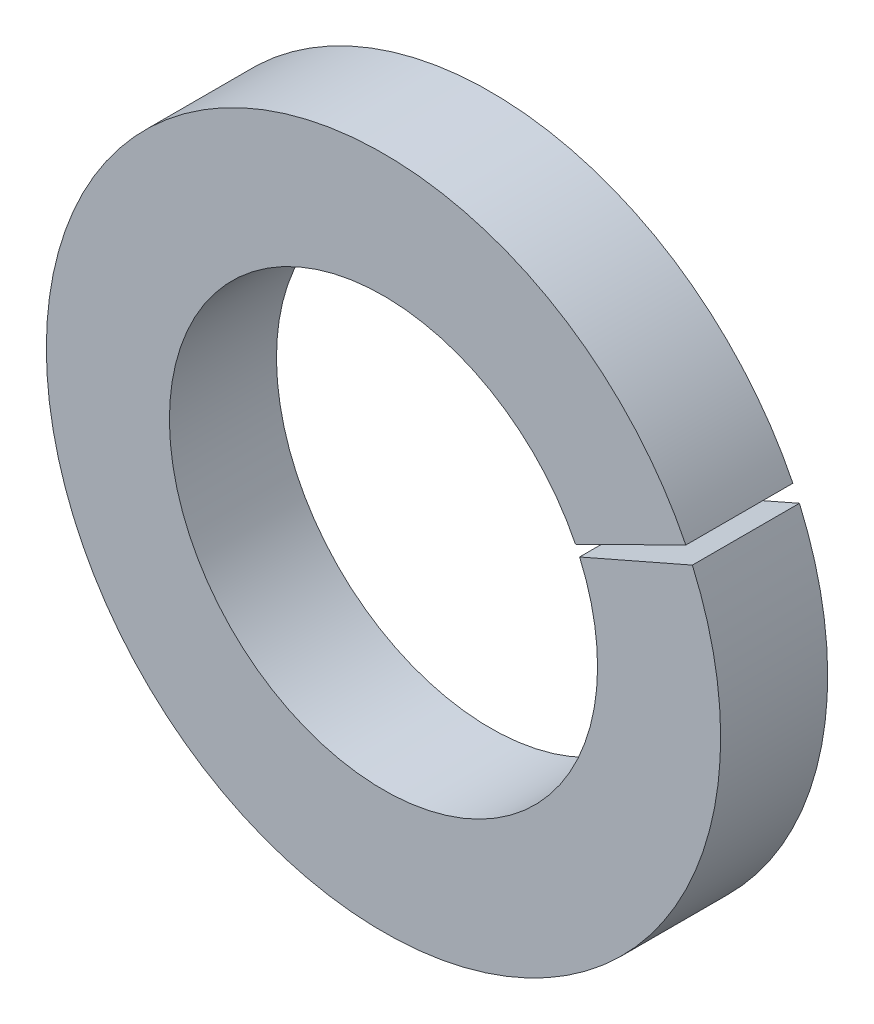
SolidWorks part; units mm, degrees
ref_plane "前视基准面" through (0, 0, 0) normal (0, 0, 1) x (1, 0, 0)
ref_plane "上视基准面" through (0, 0, 0) normal (0, 1, 0) x (1, 0, 0)
ref_plane "右视基准面" through (0, 0, 0) normal (1, 0, 0) x (0, 0, -1)
sketch "草图1" plane through (0, 0, 0) normal (0, 0, 1) x (1, 0, 0)
  circle A0 centre (0, 0) radius 3.15
  circle A1 centre (0, 0) radius 2
  dimension "D1" = 4
  dimension "D2" = 6.3
extrude "凸台-拉伸1" add sketch "草图1" along normal blind 1
sketch "草图2" plane through (0, 0, 1) normal (0, 0, 1) x (1, 0, 0)
  line L0 (0, 0) -> (4.8125, 2.3756)
  line L1 (4.8125, 2.3756) -> (4.8125, 2.1059)
  line L2 (4.8125, 2.1059) -> (0, 0)
extrude "切除-拉伸1" cut sketch "草图2" against normal blind 10
sketch "草图3" plane through (0, 0, 1) normal (0, 0, 1) x (1, 0, 0)
  circle A0 centre (0, 0) radius 2.05
  dimension "D1" = 4.1
